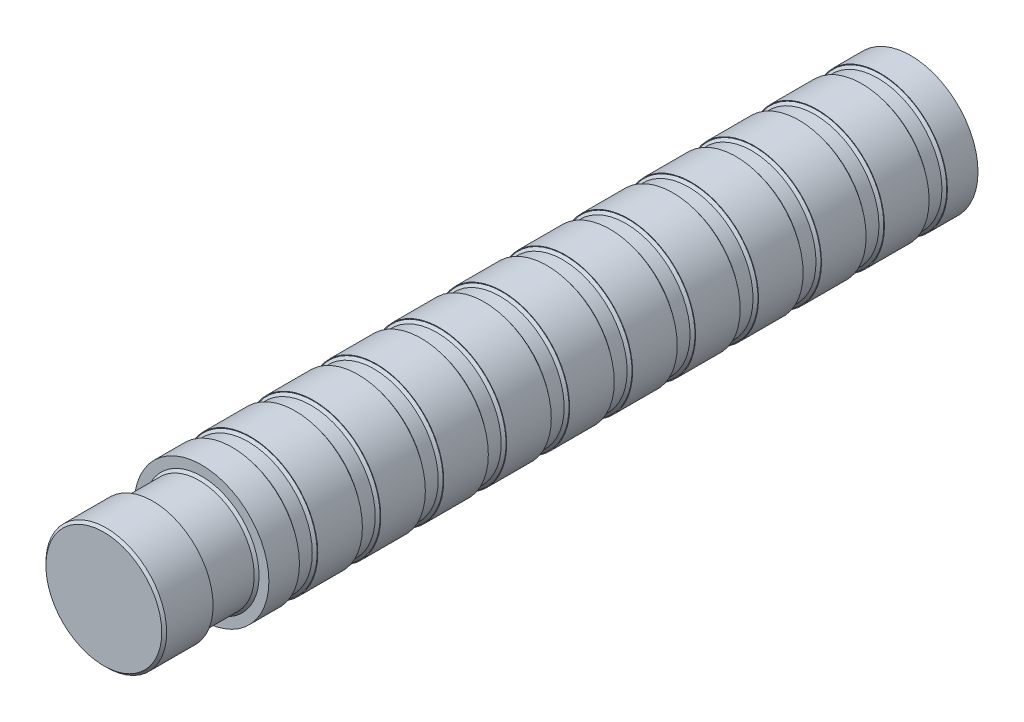
SolidWorks part; units mm, degrees
ref_plane "Front Plane" through (0, 0, 0) normal (0, 0, 1) x (1, 0, 0)
ref_plane "Top Plane" through (0, 0, 0) normal (0, 1, 0) x (1, 0, 0)
ref_plane "Right Plane" through (0, 0, 0) normal (1, 0, 0) x (0, 0, -1)
sketch "Sketch2" plane through (0, 0, 0) normal (1, 0, 0) x (0, 0, -1)
  line L0 (-29, 0) -> (29, 0)
  line L2 (-29, 5.5) -> (-26.5, 5.5)
  line L3 (29, 5.5) -> (29, 0)
  line L4 (-26.5, 5.5) -> (-26.5, 5.25)
  line L5 (-26.5, 5.25) -> (-25, 5.25)
  line L6 (-25, 5.25) -> (-25, 5.5)
  line L7 (-21.35, 5.5) -> (-21.35, 5.25)
  line L8 (-21.35, 5.25) -> (-19.85, 5.25)
  line L9 (-19.85, 5.25) -> (-19.85, 5.5)
  line L10 (-16.2, 5.5) -> (-16.2, 5.25)
  line L11 (-16.2, 5.25) -> (-14.7, 5.25)
  line L12 (-14.7, 5.25) -> (-14.7, 5.5)
  line L13 (-11.05, 5.5) -> (-11.05, 5.25)
  line L14 (-11.05, 5.25) -> (-9.55, 5.25)
  line L15 (-9.55, 5.25) -> (-9.55, 5.5)
  line L16 (-5.9, 5.5) -> (-5.9, 5.25)
  line L17 (-5.9, 5.25) -> (-4.4, 5.25)
  line L18 (-4.4, 5.25) -> (-4.4, 5.5)
  line L19 (-0.75, 5.5) -> (-0.75, 5.25)
  line L20 (-0.75, 5.25) -> (0.75, 5.25)
  line L21 (0.75, 5.25) -> (0.75, 5.5)
  line L22 (4.4, 5.5) -> (4.4, 5.25)
  line L23 (4.4, 5.25) -> (5.9, 5.25)
  line L24 (5.9, 5.25) -> (5.9, 5.5)
  line L25 (9.55, 5.5) -> (9.55, 5.25)
  line L26 (9.55, 5.25) -> (11.05, 5.25)
  line L27 (11.05, 5.25) -> (11.05, 5.5)
  line L28 (14.7, 5.5) -> (14.7, 5.25)
  line L29 (14.7, 5.25) -> (16.2, 5.25)
  line L30 (16.2, 5.25) -> (16.2, 5.5)
  line L31 (-25, 5.5) -> (-21.35, 5.5)
  line L32 (-19.85, 5.5) -> (-16.2, 5.5)
  line L33 (-14.7, 5.5) -> (-11.05, 5.5)
  line L34 (-9.55, 5.5) -> (-5.9, 5.5)
  line L35 (-4.4, 5.5) -> (-0.75, 5.5)
  line L36 (0.75, 5.5) -> (4.4, 5.5)
  line L37 (5.9, 5.5) -> (9.55, 5.5)
  line L38 (29, 0) -> (30.5762, 0) construction
  line L39 (11.05, 5.5) -> (14.7, 5.5)
  line L40 (16.2, 5.5) -> (19.85, 5.5)
  line L41 (19.85, 5.5) -> (19.85, 5.25)
  line L42 (19.85, 5.25) -> (21.35, 5.25)
  line L43 (21.35, 5.25) -> (21.35, 5.5)
  line L44 (25, 5.5) -> (25, 5.25)
  line L45 (25, 5.25) -> (26.5, 5.25)
  line L46 (26.5, 5.25) -> (26.5, 5.5)
  line L47 (21.35, 5.5) -> (25, 5.5)
  line L48 (26.5, 5.5) -> (29, 5.5)
  line L58 (-29, 5.5) -> (-29, 0)
  point P4 (0, 0)
  dimension "D1" = 58
  dimension "D2" = 2.5
  dimension "D3" = 1.5
  dimension "D4" = 0.25
  dimension "D7" = 2.5
  dimension "D8" = 3.65
  dimension "D13" = 5.5
  dimension "D6" = 11
revolve "Revolve2" add sketch "Sketch2" angle 360 about L38
sketch "Sketch3" plane through (0, 0, -29) normal (0, 0, -1) x (-1, 0, 0)
  line L0 (2.125, 0) -> (-2.125, 0) construction
  line L1 (1.475, 1.5297) -> (1.475, -1.5297)
  arc A0 (1.475, 1.5297) -> (1.475, -1.5297) centre (0, 0) ccw
  point P7 (0, 0)
  dimension "D1" = 4.25
  dimension "D2" = 3.6
extrude "Cut-Extrude1" cut sketch "Sketch3" against normal blind 14
sketch "Sketch5" plane through (0, 0, 29) normal (0, 0, 1) x (1, 0, 0)
  circle A0 centre (0, 0) radius 4.5
  dimension "D1" = 9
extrude "Boss-Extrude1" add sketch "Sketch5" along normal blind 4
sketch "Sketch6" plane through (0, 0, 33) normal (0, 0, 1) x (1, 0, 0)
  circle A0 centre (0, 0) radius 4.9375
  dimension "D1" = 9.875
extrude "Boss-Extrude2" add sketch "Sketch6" along normal blind 4
chamfer "Chamfer1" distance 0.2 angle 45 25 edges at (4.9375, 0, 37) (4.5, 0, 29) (4.5, 0, 33) (5.25, 0, 26.5) (5.25, 0, 25) (5.25, 0, 19.85) (5.25, 0, 21.35) (5.25, 0, -26.5) (5.25, 0, -25) (5.25, 0, -21.35) (5.25, 0, -19.85) (5.25, 0, -16.2) (5.25, 0, -14.7) (5.25, 0, -11.05) (5.25, 0, -9.55) (5.25, 0, -5.9) (5.25, 0, -4.4) (5.25, 0, -0.75) (5.25, 0, 0.75) (5.25, 0, 4.4) (5.25, 0, 5.9) (5.25, 0, 9.55) (5.25, 0, 11.05) (5.25, 0, 14.7) (5.25, 0, 16.2)
